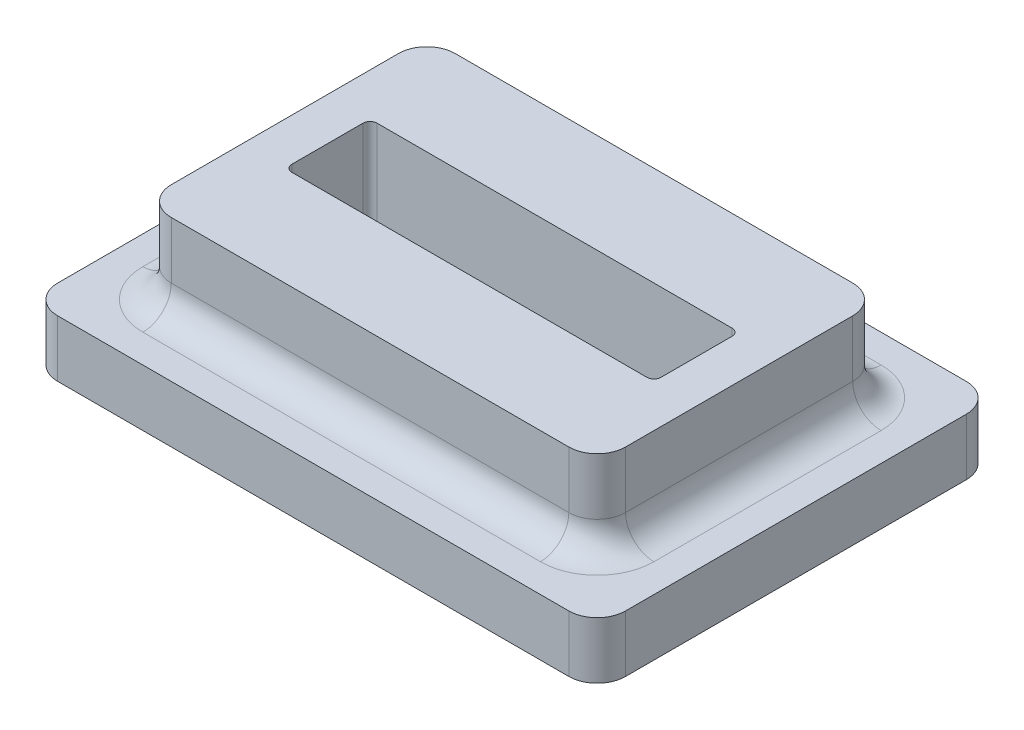
SolidWorks part; units mm, degrees
ref_plane "Front Plane" through (0, 0, 0) normal (0, 0, 1) x (1, 0, 0)
ref_plane "Top Plane" through (0, 0, 0) normal (0, 1, 0) x (1, 0, 0)
ref_plane "Right Plane" through (0, 0, 0) normal (1, 0, 0) x (0, 0, -1)
sketch "Sketch1" plane through (0, 0, 0) normal (0, 1, 0) x (1, 0, 0)
  line L1 (0, 0) -> (16, 0)
  line L2 (0, 0) -> (0, -10)
  line L3 (0, -10) -> (16, -10)
  line L4 (16, 0) -> (16, -10)
  line L6 (1.5, -6.5) -> (14.5, -6.5)
  line L7 (1.5, -3.5) -> (14.5, -3.5)
  line L8 (1.5, -3.5) -> (1.5, -6.5)
  line L9 (14.5, -3.5) -> (14.5, -6.5)
extrude "Boss-Extrude1" add sketch "Sketch1" along normal blind 3
sketch "Sketch2" plane through (0, 0, 0) normal (0, -1, 0) x (1, 0, 0)
  line L0 (0, 0) -> (0, 10) construction
  line L1 (-2, 12) -> (18, 12)
  line L2 (-2, 12) -> (-2, -2)
  line L3 (-2, -2) -> (18, -2)
  line L4 (18, 12) -> (18, -2)
  line L5 (16, 0) -> (0, 0) construction
  line L7 (1.5, 6.5) -> (14.5, 6.5)
  line L8 (1.5, 6.5) -> (1.5, 3.5)
  line L9 (1.5, 3.5) -> (14.5, 3.5)
  line L10 (14.5, 6.5) -> (14.5, 3.5)
  dimension "D1" = 20
  dimension "D2" = 14
  dimension "D3" = 2
  dimension "D4" = 2
extrude "Boss-Extrude2" add sketch "Sketch2" along normal blind 2
fillet "Fillet1" radius 1 8 edges at (8, 0, 10) (16, 1.5, 0) (16, 1.5, 10) (16, 0, 5) (0, 1.5, 10) (0, 1.5, 0) (0, 0, 5) (8, 0, 0)
fillet "Fillet2" radius 1 4 edges at (-2, -1, -2) (18, -1, -2) (18, -1, 12) (-2, -1, 12)
fillet "Fillet3" radius 0.25 4 edges at (14.5, 0.5, 6.5) (14.5, 0.5, 3.5) (1.5, 0.5, 6.5) (1.5, 0.5, 3.5)
